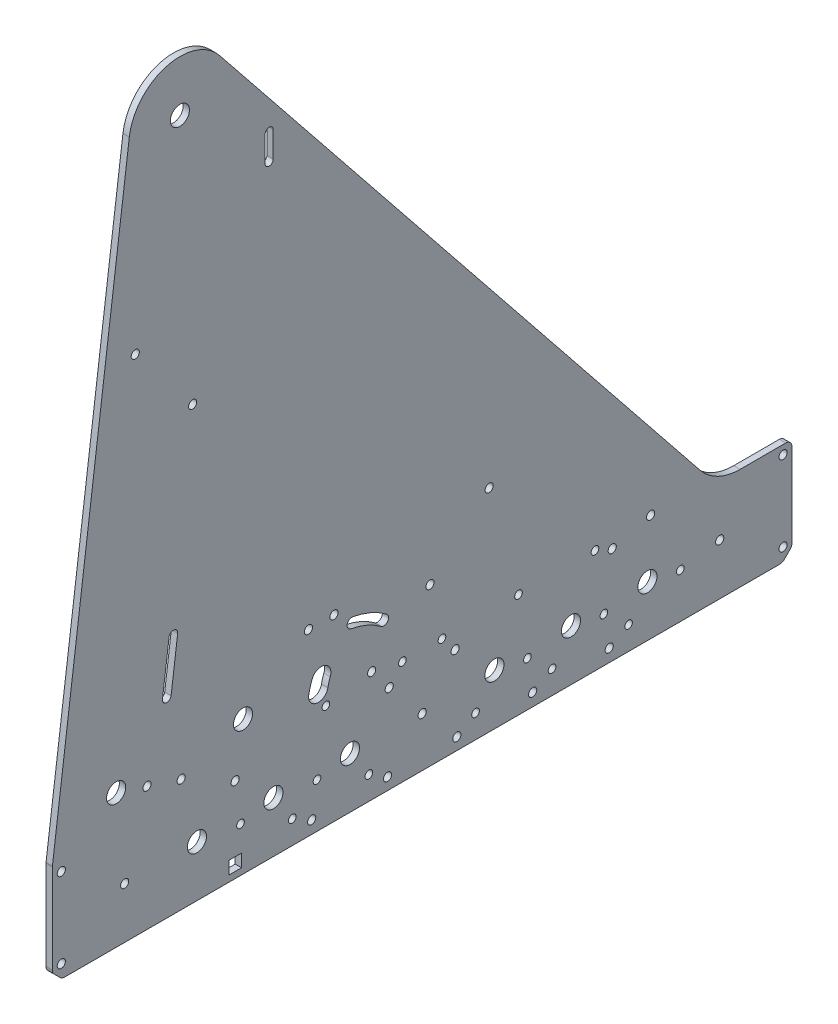
SolidWorks part; units mm, degrees
ref_plane "Front Plane" through (0, 0, 0) normal (0, 0, 1) x (1, 0, 0)
ref_plane "Top Plane" through (0, 0, 0) normal (0, 1, 0) x (1, 0, 0)
ref_plane "Right Plane" through (0, 0, 0) normal (1, 0, 0) x (0, 0, -1)
sketch "Sketch1" plane through (0, 0, 0) normal (1, 0, 0) x (0, 0, -1)
  line L0 (-184.15, -24.6062) -> (184.15, -24.6062)
  line L1 (184.15, -24.6062) -> (184.15, 26.1938)
  line L2 (184.15, 26.1938) -> (146.05, 26.1937)
  line L5 (-145.839, 321.5609) -> (-184.15, 26.1938)
  line L6 (-184.15, 26.1938) -> (-184.15, -24.6062)
  line L7 (-184.15, 350.0437) -> (184.15, 350.0437) construction
  line L9 (146.05, 26.1937) -> (-100.8314, 334.1803)
  arc A0 (-100.8314, 334.1803) -> (-145.839, 321.5609) centre (-120.65, 318.2937) ccw
  point P8 (0, -24.6062)
  dimension "D1" = 368.3
  dimension "D7" = 25.4
  dimension "D2" = 50.8
  dimension "D3" = 38.1
  dimension "D4" = 24.6062
  dimension "D5" = 374.65
  dimension "D6" = 304.8
  dimension "D8" = 342.9
extrude "Boss-Extrude1" add sketch "Sketch1" along normal blind 3.175
chamfer "Chamfer1" distance 4.7625 angle 45 2 edges at (1.5875, -24.6062, 184.15) (1.5875, -24.6062, -184.15)
fillet "Fillet1" radius 25.4 1 edges at (1.5875, 26.1937, -146.05)
fillet "Fillet2" radius 3.175 2 edges at (1.5875, 26.1938, 184.15) (1.5875, 26.1938, -184.15)
fillet "Fillet3" radius 3.175 4 edges at (1.5875, -19.8438, -184.15) (1.5875, -24.6062, -179.3875) (1.5875, -19.8437, 184.15) (1.5875, -24.6062, 179.3875)
sketch "Sketch30" plane through (3.175, 0, 0) normal (1, 0, 0) x (0, 0, -1)
  circle A8 centre (-89.211, 42.2593) radius 4.7625
  circle A9 centre (-25.1593, 30.6938) radius 2.032
  arc A10 (-51.7173, 35.4892) -> (-50.2741, 40.5715) centre (-25.1593, 30.6938) cw construction
  arc A11 (-54.7652, 42.3379) -> (-56.4665, 36.3468) centre (-25.1593, 30.6938) ccw
  arc A12 (-45.783, 38.8051) -> (-46.9681, 34.6317) centre (-25.1593, 30.6938) ccw
  arc A13 (-45.783, 38.8051) -> (-54.7652, 42.3379) centre (-50.2741, 40.5715) ccw
  arc A14 (-56.4665, 36.3468) -> (-46.9681, 34.6317) centre (-51.7173, 35.4892) ccw
  arc A15 (-34.9881, 56.6661) -> (-19.1131, 49.8125) centre (-41.7582, 19.1724) cw construction
  arc A16 (-17.6789, 51.753) -> (-34.5594, 59.0407) centre (-41.7582, 19.1724) ccw
  arc A17 (-20.5473, 47.8719) -> (-35.4169, 54.2915) centre (-41.7582, 19.1724) ccw
  arc A18 (-20.5473, 47.8719) -> (-17.6789, 51.753) centre (-19.1131, 49.8125) ccw
  arc A19 (-34.5594, 59.0407) -> (-35.4169, 54.2915) centre (-34.9881, 56.6661) ccw
  arc A20 (-19.1131, 49.8125) -> (-34.9881, 56.6661) centre (-41.7582, 19.1724) ccw construction
  circle A21 centre (94.6345, 23.8125) radius 2.032
  circle A22 centre (-56.6241, 64.5541) radius 2.032
  circle A23 centre (-43.9241, 64.5541) radius 2.032
  circle A24 centre (-56.6241, 64.5541) radius 1.905 construction
  circle A25 centre (-43.9241, 64.5541) radius 1.905 construction
  point P7 (-51.1204, 38.0658)
  point P19 (-26.6567, 54.1518)
  dimension "D2" = 9.652
  dimension "D4" = 4.064
  dimension "D1" = 4.064
  dimension ".375" = 9.525
  dimension "D3" = 4.826
extrude "Cut-Extrude9" cut sketch "Sketch30" against normal through all
sketch "Sketch16" plane through (3.175, 0, 0) normal (1, 0, 0) x (0, 0, -1)
  circle A0 centre (112.1746, 0.7937) radius 4.7625
  circle A1 centre (74.0746, 0.7937) radius 4.7625
  circle A2 centre (35.9746, 0.7937) radius 4.7625
  circle A3 centre (-35.9746, 0.7938) radius 4.7625
  circle A4 centre (-74.0746, 0.7938) radius 4.7625
  circle A5 centre (-112.1746, 0.7937) radius 4.7625
  dimension "D1" = 9.525
  dimension "D2" = 9.525
extrude "Cut-Extrude1" cut sketch "Sketch16" against normal up to next
sketch "Sketch25" plane through (3.175, 0, 0) normal (1, 0, 0) x (0, 0, -1)
  circle A0 centre (102.7672, -13.0003) radius 1.905 construction
  circle A1 centre (86.0486, 27.3622) radius 1.905 construction
  circle A2 centre (128.5804, -2.3081) radius 1.905 construction
  circle A3 centre (102.7672, -13.0003) radius 1.905
  circle A4 centre (86.0486, 27.3622) radius 1.905
  circle A5 centre (128.5804, -2.3081) radius 1.905
  circle A6 centre (64.6672, -13.0003) radius 1.905 construction
  circle A8 centre (-9.8486, 27.3622) radius 1.905 construction
  circle A10 centre (-47.9486, 27.3622) radius 1.905 construction
  circle A11 centre (-90.4804, -2.3081) radius 1.905 construction
  circle A12 centre (-64.6672, -13.0003) radius 1.905 construction
  circle A14 centre (-52.3804, -2.3081) radius 1.905 construction
  circle A15 centre (-26.5672, -13.0003) radius 1.905 construction
  circle A16 centre (9.8486, 27.3622) radius 1.905 construction
  circle A17 centre (26.5672, -13.0003) radius 1.905 construction
  circle A18 centre (47.9486, 27.3622) radius 1.905 construction
  circle A19 centre (52.3804, -2.3081) radius 1.905 construction
  circle A20 centre (90.4804, -2.3081) radius 1.905 construction
  circle A21 centre (-9.8486, 27.3622) radius 1.905
  circle A23 centre (-47.9486, 27.3622) radius 1.905
  circle A24 centre (-90.4804, -2.3081) radius 1.905
  circle A25 centre (-64.6672, -13.0003) radius 1.905
  circle A27 centre (-52.3804, -2.3081) radius 1.905
  circle A28 centre (-26.5672, -13.0003) radius 1.905
  circle A29 centre (9.8486, 27.3622) radius 1.905
  circle A30 centre (26.5672, -13.0003) radius 1.905
  circle A31 centre (47.9486, 27.3622) radius 1.905
  circle A32 centre (64.6672, -13.0003) radius 1.905
  circle A33 centre (52.3804, -2.3081) radius 1.905
  circle A34 centre (90.4804, -2.3081) radius 1.905
extrude "Cut-Extrude4" cut sketch "Sketch25" against normal up to next
sketch "Sketch23" plane through (3.175, 0, 0) normal (1, 0, 0) x (0, 0, -1)
  circle A0 centre (179.705, 21.7488) radius 1.905 construction
  point P0 (-55.0246, -18.3223)
  point P6 (-93.1246, 17.5943)
  point P9 (-17.2515, -18.6426)
  point P12 (-16.4124, 19.3854)
  point P15 (16.4124, 19.3854)
  point P18 (17.2515, -18.6426)
  point P21 (55.0246, -18.3223)
  point P35 (3.8736, 53.6853)
  point P38 (113.7728, 28.6594)
  point P41 (-137.0088, 37.226)
  point P44 (-179.705, 21.7487)
  point P47 (-179.705, -18.0026)
  point P50 (179.705, 21.7488)
  point P53 (179.705, -18.0026)
  point P59 (93.1246, -18.3223)
hole_wizard "#8 (0.16) Diameter Hole1" positions "Sketch23" profile "Sketch24" hole size "#8" standard "ANSI Inch" end condition up to next
sketch "Sketch24" plane through (3.175, -18.3223, 55.0246) normal (0, 1, 0) x (0, 0, -1)
  line L0 (0, 0) -> (0, 3.175)
  line L1 (0, 3.175) -> (2.032, 3.175)
  line L2 (2.032, 3.175) -> (2.032, 0)
  line L5 (2.032, 0) -> (0, 0)
  line L11 (0, -6.35) -> (0, 107.95) construction
  dimension "Thru Hole Dia." = 4.064
  dimension "Thru Hole Depth" = 3.175
sketch "Sketch22" plane through (3.175, 0, 0) normal (1, 0, 0) x (0, 0, -1)
  line L0 (-96.2996, -15.1473) -> (-89.9496, -15.1473) construction
  line L1 (-96.2996, -15.1473) -> (-89.9496, -15.1473)
  line L2 (-96.2996, -15.1473) -> (-96.2996, -21.4973)
  line L3 (-96.2996, -21.4973) -> (-89.9496, -21.4973)
  line L4 (-89.9496, -15.1473) -> (-89.9496, -21.4973)
  line L5 (-96.2996, -15.1473) -> (-89.9496, -21.4973) construction
  line L6 (-96.2996, -21.4973) -> (-89.9496, -15.1473) construction
  line L7 (-89.9496, -15.1473) -> (-89.9496, -19.8734) construction
  point P0 (-93.1246, -18.3223)
  dimension "D1" = 6.35
extrude "Cut-Extrude3" cut sketch "Sketch22" against normal up to next
sketch "Sketch21" plane through (3.175, 0, 0) normal (1, 0, 0) x (0, 0, -1)
  circle A0 centre (-148.1579, 0.7937) radius 2.032
  circle A2 centre (0, 0) radius 2.032
  circle A3 centre (148.1579, 0.7938) radius 2.032
  dimension "D1" = 4.064
extrude "Cut-Extrude2" cut sketch "Sketch21" against normal up to next
sketch "Sketch26" [suppressed] plane through (3.175, 0, 0) normal (1, 0, 0) x (0, 0, -1)
  line L0 (-145.839, 321.5609) -> (-184.1236, 26.3971) construction
  line L1 (-178.0724, -24.6062) -> (178.0724, -24.6062) construction
  circle A0 centre (-121.0218, 216.6937) radius 15.24
  dimension "D1" = 30.48
  dimension "D2" = 38.1
  dimension "D3" = 241.3
extrude "Cut-Extrude5" [suppressed] cut sketch "Sketch26" against normal through all
sketch "Sketch27" plane through (3.175, 0, 0) normal (1, 0, 0) x (0, 0, -1)
  circle A0 centre (-120.65, 318.2937) radius 4.7625
  dimension "D1" = 9.525
extrude "Cut-Extrude6" cut sketch "Sketch27" against normal through all
sketch "Sketch28" plane through (3.175, 0, 0) normal (1, 0, 0) x (0, 0, -1)
  line L0 (-120.65, 318.2937) -> (-103.5612, 277.2599) construction
  line L1 (-103.5612, 277.2599) -> (-86.3654, 258.566) construction
  line L2 (-86.3654, 258.566) -> (-90.1612, 246.4465) construction
  line L3 (-90.1612, 246.4465) -> (-93.9569, 234.327) construction
  line L4 (-145.839, 321.5609) -> (-184.1236, 26.3971) construction
  circle A0 centre (-93.9569, 234.327) radius 2.032
  circle A1 centre (-90.1612, 246.4465) radius 2.032
  circle A2 centre (-86.3654, 258.566) radius 2.0955
  circle A3 centre (-103.5612, 277.2599) radius 2.032
  dimension "D4" = 4.064
  dimension "D5" = 4.191
  dimension "D6" = 4.064
  dimension "D1" = 25.4
  dimension "D2" = 44.45
  dimension "D3" = 12.7
  dimension "D7" = 30
  dimension "D8" = 120
  dimension "D9" = 160
extrude "Cut-Extrude7" [suppressed] cut sketch "Sketch28" against normal through all
sketch "Sketch29" plane through (3.175, 0, 0) normal (1, 0, 0) x (0, 0, -1)
  line L1 (-76.2, 288.925) -> (-76.2, 276.225) construction
  line L2 (-74.168, 288.925) -> (-74.168, 276.225)
  line L3 (-78.232, 288.925) -> (-78.232, 276.225)
  arc A4 (-74.168, 288.925) -> (-78.232, 288.925) centre (-76.2, 288.925) ccw
  arc A5 (-78.232, 276.225) -> (-74.168, 276.225) centre (-76.2, 276.225) ccw
  point P8 (-76.2, 282.575)
  dimension "D1" = 276.225
  dimension "D2" = 2.032
  dimension "D3" = 76.2
  dimension "D4" = 12.7
sketch "Sketch31" plane through (0, 0, 0) normal (-1, 0, 0) x (0, 0, 1)
  circle A1 centre (114.3, 190.5) radius 2.032
  dimension "D1" = 114.3
  dimension "D6" = 4.064
  dimension "D2" = 190.5
extrude "Cut-Extrude10" cut sketch "Sketch31" against normal through all
sketch "Sketch34" plane through (0, 0, 0) normal (-1, 0, 0) x (0, 0, 1)
  line L3 (123.9045, 95.7355) -> (127.1716, 70.5465) construction
  line L4 (126.0455, 96.0132) -> (129.3127, 70.8242)
  line L5 (121.7634, 95.4578) -> (125.0306, 70.2688)
  line L6 (145.839, 321.5609) -> (184.1236, 26.3971) construction
  arc A2 (126.0455, 96.0132) -> (121.7634, 95.4578) centre (123.9045, 95.7355) ccw
  arc A3 (125.0306, 70.2688) -> (129.3127, 70.8242) centre (127.1716, 70.5465) ccw
  point P9 (125.538, 83.141)
  point P18 (114.3, 190.5)
  dimension "D8" = 4.318
  dimension "D6" = 50.8
  dimension "D7" = 25.4
  dimension "D9" = 95.25
extrude "Cut-Extrude12" cut sketch "Sketch34" against normal through all
sketch "Sketch38" plane through (3.175, 0, 0) normal (1, 0, 0) x (0, 0, -1)
  line L0 (-184.15, 25.9887) -> (-184.15, -18.5286) construction
  line L1 (-178.0724, -24.6062) -> (178.0724, -24.6062) construction
  circle A0 centre (-152.4, 42.0688) radius 4.7625
  dimension "D1" = 31.75
  dimension "D3" = 9.525
  dimension "D2" = 66.675
extrude "Cut-Extrude14" cut sketch "Sketch38" against normal through all
sketch "Sketch37" plane through (3.175, 0, 0) normal (1, 0, 0) x (0, 0, -1)
  circle A0 centre (33.3375, 80.645) radius 2.032
  circle A8 centre (0, 0) radius 2.032 construction
  dimension "D1" = 4.064
  dimension "D2" = 33.3375
  dimension "D3" = 80.645
extrude "Cut-Extrude13" cut sketch "Sketch37" against normal through all
extrude "Cut-Extrude15" cut sketch "Sketch29" against normal through all
sketch "Sketch40" plane through (3.175, 0, 0) normal (1, 0, 0) x (0, 0, -1)
  circle A0 centre (-120.015, 31.75) radius 2.032
  dimension "D1" = 4.064
  dimension "D2" = 120.015
  dimension "D3" = 31.75
extrude "Cut-Extrude16" cut sketch "Sketch40" against normal through all
sketch "Sketch41" [suppressed] plane through (3.175, 0, 0) normal (1, 0, 0) x (0, 0, -1)
  line L0 (-120.65, 318.2937) -> (-98.425, 279.7989) construction
  line L1 (-98.425, 279.7989) -> (-77.6666, 265.1617) construction
  line L2 (-120.65, 318.2937) -> (-60.41, 318.2937) construction
  circle A0 centre (-120.65, 318.2937) radius 25.4 construction
  circle A1 centre (-98.425, 279.7989) radius 19.05 construction
  circle A2 centre (-77.6666, 265.1617) radius 6.35 construction
  circle A3 centre (-98.425, 279.7989) radius 2.032
  circle A4 centre (-77.6666, 265.1617) radius 2.032
  dimension "D1" = 50.8
  dimension "D2" = 38.1
  dimension "D3" = 12.7
  dimension "D4" = 4.064
  dimension "D5" = 60
extrude "Cut-Extrude17" [suppressed] cut sketch "Sketch41" against normal through all
sketch "Sketch43" plane through (3.175, 0, 0) normal (1, 0, 0) x (0, 0, -1)
  line L0 (-152.4, 200.025) -> (-123.6487, 200.025) construction
  line L1 (-115.9779, 252.0412) -> (-152.4, 200.025) construction
  circle A0 centre (-152.4, 200.025) radius 2.032
  arc A1 (-143.2813, 262.8669) -> (-96.4668, 230.087) centre (-152.4, 200.025) cw construction
  arc A2 (-92.2158, 232.3717) -> (-142.5883, 267.6428) centre (-152.4, 200.025) ccw
  arc A3 (-100.7177, 227.8023) -> (-143.9743, 258.0909) centre (-152.4, 200.025) ccw
  arc A4 (-100.7177, 227.8023) -> (-92.2158, 232.3717) centre (-96.4668, 230.087) ccw
  arc A5 (-142.5883, 267.6428) -> (-143.9743, 258.0909) centre (-143.2813, 262.8669) ccw
  point P6 (-115.9779, 252.0412)
  dimension "D1" = 4.064
  dimension "D4" = 4.826
  dimension "D2" = 200.025
  dimension "D3" = 152.4
  dimension "D5" = 63.5
  dimension "D6" = 57.15
  dimension "D7" = 55
extrude "Cut-Extrude19" [suppressed] cut sketch "Sketch43" against normal through all
sketch "Sketch44" plane through (3.175, 0, 0) normal (1, 0, 0) x (0, 0, -1)
  circle A0 centre (-142.875, 226.3775) radius 2.032
  dimension "D1" = 4.064
  dimension "D2" = 142.875
  dimension "D3" = 226.3775
extrude "Cut-Extrude20" cut sketch "Sketch44" against normal through all
sketch "Sketch50" [suppressed] plane through (0, 0, 0) normal (-1, 0, 0) x (0, 0, 1)
  line L0 (98.7055, 213.2489) -> (51.4524, 213.2489) construction
  line L1 (98.7055, 211.2169) -> (51.4524, 211.2169)
  line L2 (98.7055, 215.2809) -> (51.4524, 215.2809)
  arc A1 (98.7055, 211.2169) -> (98.7055, 215.2809) centre (98.7055, 213.2489) ccw
  arc A2 (51.4524, 215.2809) -> (51.4524, 211.2169) centre (51.4524, 213.2489) ccw
  point P3 (75.079, 213.2489)
  dimension "D1" = 2.032
  dimension "D2" = 98.7055
  dimension "D3" = 213.2489
  dimension "D4" = 47.253
extrude "Cut-Extrude22" [suppressed] cut sketch "Sketch50" against normal through all
sketch "Sketch51" [suppressed] plane through (3.175, 0, 0) normal (1, 0, 0) x (0, 0, -1)
  circle A0 centre (-114.3, 222.6469) radius 2.032
  circle A1 centre (-114.3, 190.8969) radius 2.032
  dimension "D1" = 222.6469
  dimension "D3" = 31.75
  dimension "D4" = 4.064
  dimension "D2" = 114.3
extrude "Cut-Extrude23" [suppressed] cut sketch "Sketch51" against normal through all
sketch "Sketch52" [suppressed] plane through (0, 0, 0) normal (-1, 0, 0) x (0, 0, 1)
  arc A5 (141.2875, 264.4775) -> (109.814, 245.1467) centre (142.9767, 226.44) ccw construction
  arc A6 (141.1974, 266.5075) -> (108.0442, 246.1451) centre (142.9767, 226.44) ccw
  arc A7 (141.3776, 262.4475) -> (111.5838, 244.1484) centre (142.9767, 226.44) ccw
  arc A8 (141.3776, 262.4475) -> (141.1974, 266.5075) centre (141.2875, 264.4775) ccw
  arc A9 (108.0442, 246.1451) -> (111.5838, 244.1484) centre (109.814, 245.1467) ccw
  point P4 (123.0497, 258.8841)
  dimension "D1" = 38.075
  dimension "D2" = 2.032
  dimension "D3" = 264.4775
  dimension "D4" = 141.2875
  dimension "D5" = 245.1467
  dimension "D6" = 109.814
extrude "Cut-Extrude24" [suppressed] cut sketch "Sketch52" against normal through all
sketch "Sketch53" [suppressed] plane through (3.175, 0, 0) normal (1, 0, 0) x (0, 0, -1)
  line L0 (-35.2284, 197.2663) -> (-35.2284, 135.876) construction
  line L1 (-33.1964, 197.2663) -> (-33.1964, 135.876)
  line L2 (-37.2604, 197.2663) -> (-37.2604, 135.876)
  arc A0 (-33.1964, 197.2663) -> (-37.2604, 197.2663) centre (-35.2284, 197.2663) ccw
  arc A1 (-37.2604, 135.876) -> (-33.1964, 135.876) centre (-35.2284, 135.876) ccw
  point P2 (-35.2284, 166.5712)
  dimension "D1" = 2.032
  dimension "D2" = 61.3903
  dimension "D3" = 197.2663
  dimension "D4" = 35.2284
extrude "Cut-Extrude25" [suppressed] cut sketch "Sketch53" against normal through all
